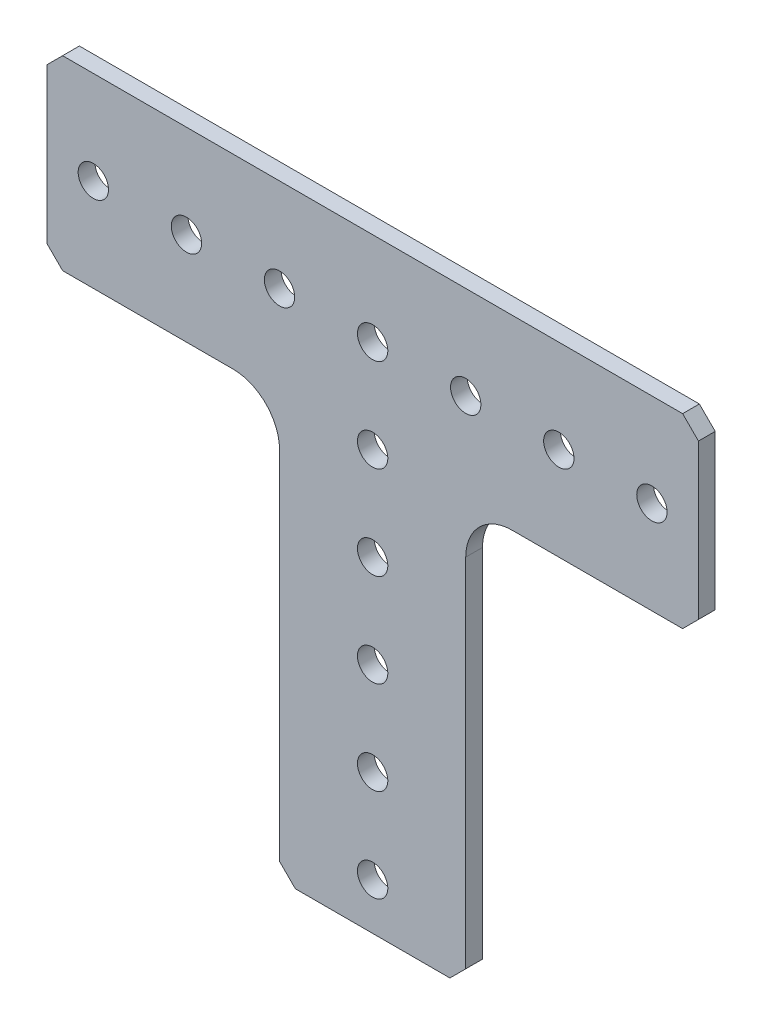
SolidWorks part; units mm, degrees
ref_plane "Front Plane" through (0, 0, 0) normal (0, 0, 1) x (1, 0, 0)
ref_plane "Top Plane" through (0, 0, 0) normal (0, 1, 0) x (1, 0, 0)
ref_plane "Right Plane" through (0, 0, 0) normal (1, 0, 0) x (0, 0, -1)
ref_plane "Plane1" through (0, 0, 2.286) normal (0, 0, 1) x (1, 0, 0)
sketch "Sketch1" plane through (0, 0, 2.286) normal (0, 0, 1) x (1, 0, 0)
  line L0 (12.7, -54.991) -> (12.7, -6.35)
  line L1 (19.05, 0) -> (42.291, 0)
  line L2 (42.291, 0) -> (44.45, 2.159)
  line L3 (44.45, 2.159) -> (44.45, 23.241)
  line L4 (44.45, 23.241) -> (42.291, 25.4)
  line L5 (42.291, 25.4) -> (-42.291, 25.4)
  line L6 (-42.291, 25.4) -> (-44.45, 23.241)
  line L7 (-44.45, 23.241) -> (-44.45, 2.159)
  line L8 (-44.45, 2.159) -> (-42.291, 0)
  line L9 (-42.291, 0) -> (-19.05, 0)
  line L10 (-12.7, -6.35) -> (-12.7, -54.991)
  line L11 (-12.7, -54.991) -> (-10.541, -57.15)
  line L12 (-10.541, -57.15) -> (10.541, -57.15)
  line L13 (10.541, -57.15) -> (12.7, -54.991)
  circle A0 centre (0, -38.1) radius 2.0701
  circle A1 centre (0, -12.7) radius 2.0701
  circle A2 centre (38.1, 12.7) radius 2.0701
  circle A3 centre (12.7, 12.7) radius 2.0701
  circle A4 centre (-12.7, 12.7) radius 2.0701
  circle A5 centre (-38.1, 12.7) radius 2.0701
  circle A6 centre (-25.4, 12.7) radius 2.0701
  circle A7 centre (0, 12.7) radius 2.0701
  circle A8 centre (25.4, 12.7) radius 2.0701
  circle A9 centre (0, 0) radius 2.0701
  circle A10 centre (0, -25.4) radius 2.0701
  circle A11 centre (0, -50.8) radius 2.0701
  arc A12 (12.7, -6.35) -> (19.05, 0) centre (19.05, -6.35) cw
  arc A13 (-19.05, 0) -> (-12.7, -6.35) centre (-19.05, -6.35) cw
  dimension "D1" = 4.1402
extrude "Boss-Extrude1" add sketch "Sketch1" against normal blind 2.286
